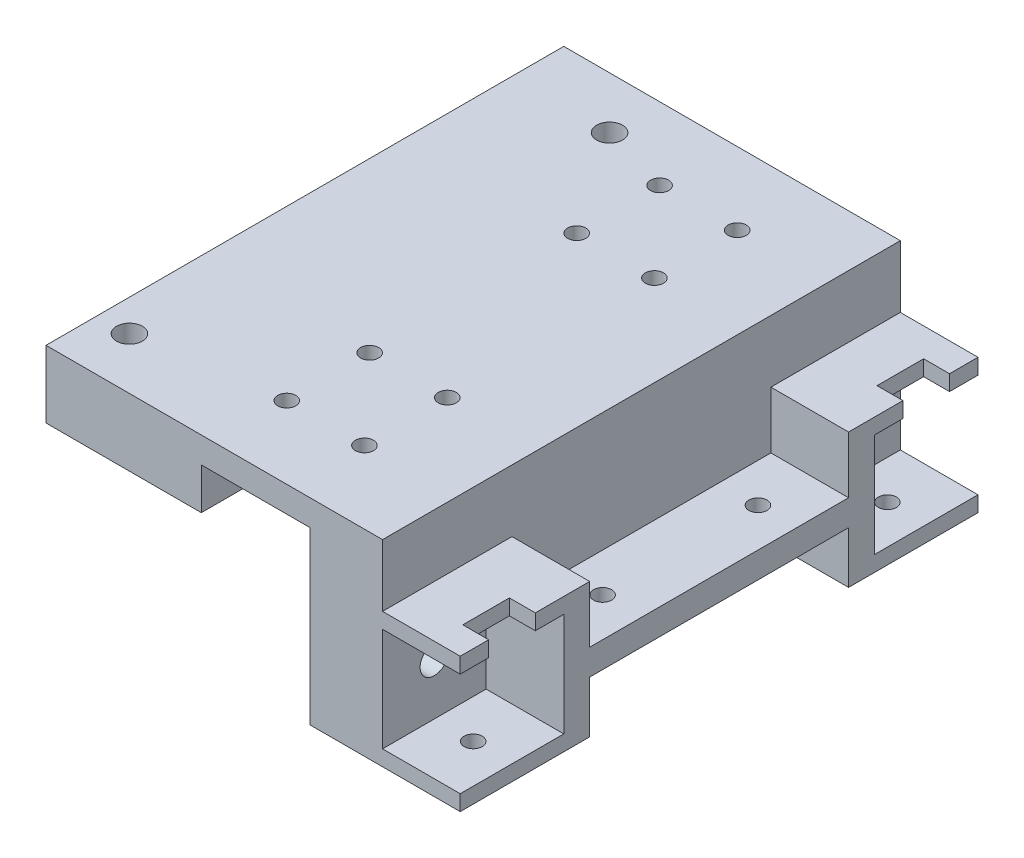
SolidWorks part; units mm, degrees
ref_plane "Front Plane" through (0, 0, 0) normal (0, 0, 1) x (1, 0, 0)
ref_plane "Top Plane" through (0, 0, 0) normal (0, 1, 0) x (1, 0, 0)
ref_plane "Right Plane" through (0, 0, 0) normal (1, 0, 0) x (0, 0, -1)
sketch "Sketch1" plane through (0, 0, 0) normal (0, 1, 0) x (1, 0, 0)
  line L0 (0, 50) -> (0, -50) construction
  line L1 (-10, 50) -> (10, 50)
  line L2 (-10, 50) -> (-10, -50)
  line L3 (-10, -50) -> (10, -50)
  line L4 (10, 50) -> (10, -50) construction
  line L5 (-10, 50) -> (10, -50) construction
  line L6 (-10, -50) -> (10, 50) construction
  line L7 (-7.5, 36) -> (7.5, 36) construction
  line L8 (-7.5, 36) -> (7.5, 20) construction
  line L9 (-10, 0) -> (10, 0) construction
  line L10 (-7.5, -36) -> (7.5, -20) construction
  line L11 (-7.5, -36) -> (7.5, -36) construction
  line L12 (-7.5, 20) -> (7.5, 20) construction
  line L13 (10, 50) -> (11, 50)
  line L14 (11, 50) -> (11, -50)
  line L15 (11, -50) -> (10, -50)
  circle A0 centre (-7.5, 36) radius 1.75
  circle A1 centre (7.5, 36) radius 1.75
  circle A2 centre (-7.5, 20) radius 1.75
  circle A3 centre (7.5, 20) radius 1.75
  circle A4 centre (7.5, -20) radius 1.75
  circle A5 centre (-7.5, -20) radius 1.75
  circle A6 centre (7.5, -36) radius 1.75
  circle A7 centre (-7.5, -36) radius 1.75
  point P0 (0, 0)
  point P16 (0, 36)
  dimension "D2" = 3.5
  dimension "D1" = 20
  dimension "D3" = 15
  dimension "D4" = 16
  dimension "D5" = 100
  dimension "D6" = 20
  dimension "D7" = 1
extrude "Boss-Extrude1" add sketch "Sketch1" along normal blind 5
sketch "Sketch2" plane through (11, 0, 0) normal (1, 0, 0) x (0, 0, -1)
  line L1 (-50, 5) -> (50, 5)
  line L2 (-50, 5) -> (-50, -33)
  line L3 (-50, -33) -> (50, -33)
  line L5 (50, 5) -> (50, -33)
  line L6 (50, 5) -> (50, 0) construction
  line L7 (-50, 5) -> (-50, 0) construction
  line L8 (-50, 5) -> (50, 5) construction
  dimension "D1" = 38
extrude "Boss-Extrude2" add sketch "Sketch2" along normal blind 14
sketch "Sketch3" plane through (25, 0, 0) normal (1, 0, 0) x (0, 0, -1)
  line L0 (0, 5) -> (0, -33) construction
  line L1 (-25, -18) -> (25, -18)
  line L2 (-25, -18) -> (-25, -23)
  line L3 (-25, -23) -> (25, -23)
  line L4 (25, -18) -> (25, -23)
  line L5 (50, 5) -> (-50, 5) construction
  line L6 (-50, -33) -> (50, -33) construction
  point P10 (0, -18)
  dimension "D1" = 5
  dimension "D2" = 50
  dimension "D3" = 10
extrude "Boss-Extrude3" add sketch "Sketch3" along normal blind 15
sketch "Sketch4" plane through (0, -18, 0) normal (0, 1, 0) x (1, 0, 0)
  line L0 (25, 0) -> (40, 0) construction
  line L1 (25, 25) -> (25, -25) construction
  line L2 (40, 25) -> (40, -25) construction
  line L3 (32.5, -15) -> (32.5, 15) construction
  circle A0 centre (32.5, 15) radius 1.75
  circle A1 centre (32.5, -15) radius 1.75
  point P8 (32.5, 0)
  dimension "D1" = 30
  dimension "D2" = 3.5
extrude "Cut-Extrude1" cut sketch "Sketch4" against normal through all
sketch "Sketch8" plane through (25, 0, 0) normal (1, 0, 0) x (0, 0, -1)
  line L0 (-50, 5) -> (-50, -33) construction
  line L1 (-50, -7) -> (-25, -7)
  line L2 (-50, -7) -> (-50, -10)
  line L3 (-50, -33) -> (-25, -33)
  line L4 (-25, -7) -> (-25, -33)
  line L5 (-50, -30) -> (-50, -33)
  line L6 (-50, -30) -> (-30, -30)
  line L8 (-50, -10) -> (-30, -10)
  line L9 (-30, -30) -> (-30, -10)
  line L10 (0, 19.25) -> (0, -19.25) construction
  line L11 (30, -30) -> (30, -10)
  line L12 (50, -10) -> (30, -10)
  line L13 (50, -30) -> (30, -30)
  line L14 (50, -30) -> (50, -33)
  line L15 (25, -7) -> (25, -33)
  line L16 (50, -33) -> (25, -33)
  line L17 (50, -7) -> (50, -10)
  line L18 (50, -7) -> (25, -7)
  line L19 (-50, -33) -> (50, -33) construction
  dimension "D1" = 3
  dimension "D2" = 5
  dimension "D3" = 3
  dimension "D4" = 20
  dimension "D5" = 20
extrude "Boss-Extrude6" add sketch "Sketch8" along normal blind 15
sketch "Sketch9" plane through (25, 0, 0) normal (1, 0, 0) x (0, 0, -1)
  line L0 (-50, -10) -> (-30, -30) construction
  line L1 (50, -10) -> (30, -30) construction
  circle A0 centre (-40, -20) radius 2.75
  circle A1 centre (40, -20) radius 2.75
  dimension "D1" = 5.5
extrude "Cut-Extrude3" cut sketch "Sketch9" against normal through all
sketch "Sketch10" plane through (11, 0, 0) normal (-1, 0, 0) x (0, 0, 1)
  circle A0 centre (-40, -20) radius 4.5
  circle A1 centre (40, -20) radius 4.5
  dimension "D1" = 9
extrude "Cut-Extrude4" cut sketch "Sketch10" against normal offset from surface (9 mm away) 5 up to face at (25, -20, 37.25)
sketch "Sketch11" plane through (0, -7, 0) normal (0, 1, 0) x (1, 0, 0)
  line L0 (40, -25) -> (40, -50) construction
  line L1 (40, -35.5) -> (35, -35.5)
  line L2 (40, -35.5) -> (40, -44.5)
  line L3 (40, -44.5) -> (35, -44.5)
  line L4 (35, -35.5) -> (35, -44.5)
  line L5 (35, -40) -> (40, -40) construction
  line L6 (40, -50) -> (25, -50) construction
  line L7 (-10, 0) -> (40, 0) construction
  line L8 (-10, 50) -> (-10, -50) construction
  line L9 (40, 25) -> (40, -25) construction
  line L10 (40, -35.5) -> (35, -35.5)
  line L11 (40, -44.5) -> (35, -44.5)
  line L12 (35, 40) -> (40, 40) construction
  line L13 (40, 44.5) -> (35, 44.5)
  line L14 (40, 35.5) -> (35, 35.5)
  line L15 (35, 35.5) -> (35, 44.5)
  line L16 (40, 44.5) -> (35, 44.5)
  line L17 (40, 35.5) -> (40, 44.5)
  line L18 (40, 35.5) -> (35, 35.5)
  line M7 (40, -50) -> (40, -25)
  dimension "D1" = 9
  dimension "D2" = 10
  dimension "D3" = 5
extrude "Cut-Extrude5" cut sketch "Sketch11" against normal up to next contours L1 L4 L3 M7 | L14 L17 L13 L15 region at (37.5, -7, 40) region at (37.5, -7, -40)
sketch "Sketch12" plane through (0, -30, 0) normal (0, 1, 0) x (1, 0, 0)
  line L0 (40, -40) -> (25, -40) construction
  line L1 (40, -30) -> (40, -50) construction
  line L2 (25, -25) -> (25, -50) construction
  line L3 (-19.25, 0) -> (19.25, 0) construction
  circle A0 centre (32.5, -40) radius 1.75
  circle A2 centre (32.5, 40) radius 1.75
  dimension "D1" = 3.5
extrude "Cut-Extrude6" cut sketch "Sketch12" against normal through all
sketch "Sketch13" plane through (-10, 0, 0) normal (-1, 0, 0) x (0, 0, 1)
  line L1 (-50, 5) -> (50, 5)
  line L2 (-50, 5) -> (-50, -8)
  line L3 (-50, -8) -> (50, -8)
  line L4 (50, 5) -> (50, -8)
  dimension "D1" = 13
extrude "Boss-Extrude7" add sketch "Sketch13" along normal blind 30
sketch "Sketch14" plane through (0, 5, 0) normal (0, 1, 0) x (1, 0, 0)
  line L0 (-40, -50) -> (25, -50) construction
  line L1 (-10.5, -50) -> (10.5, -50) construction
  line L2 (-10.5, -50) -> (-10.5, 50) construction
  line L3 (-10.5, 50) -> (10.5, 50) construction
  line L4 (10.5, -50) -> (10.5, 50) construction
  line L5 (25, 50) -> (-40, 50) construction
  line L6 (-27.5162, 40) -> (-27.5162, -40) construction
  line L7 (25, 50) -> (25, -50) construction
  line L8 (-40, 50) -> (25, 50) construction
  line L9 (-40, 50) -> (-40, 30) construction
  line L10 (-40, 30) -> (25, 30) construction
  line L11 (25, 50) -> (25, 30) construction
  line L12 (-40, 40) -> (25, 40) construction
  line L13 (-40, -50) -> (-40, 50) construction
  line L14 (-40, -30) -> (25, -30) construction
  line L15 (-40, -30) -> (-40, -50) construction
  line L16 (-40, -50) -> (25, -50) construction
  line L17 (25, -30) -> (25, -50) construction
  line L18 (-40, -40) -> (25, -40) construction
  circle A0 centre (-21.15, 40) radius 2.5
  circle A1 centre (-33.8824, -40) radius 2.5
  circle A2 centre (-33.8824, -40) radius 6.3662 construction
  circle A3 centre (-21.15, 40) radius 6.3662 construction
  point P14 (0, 50)
  point P36 (-33.8824, -40)
  dimension "D1" = 5
  dimension "D2" = 5
  dimension "D4" = 21
  dimension "D5" = 12.7324
  dimension "D6" = 20
  dimension "D3" = 21.15
  dimension "D7" = 20
extrude "Cut-Extrude7" cut sketch "Sketch14" against normal through all
